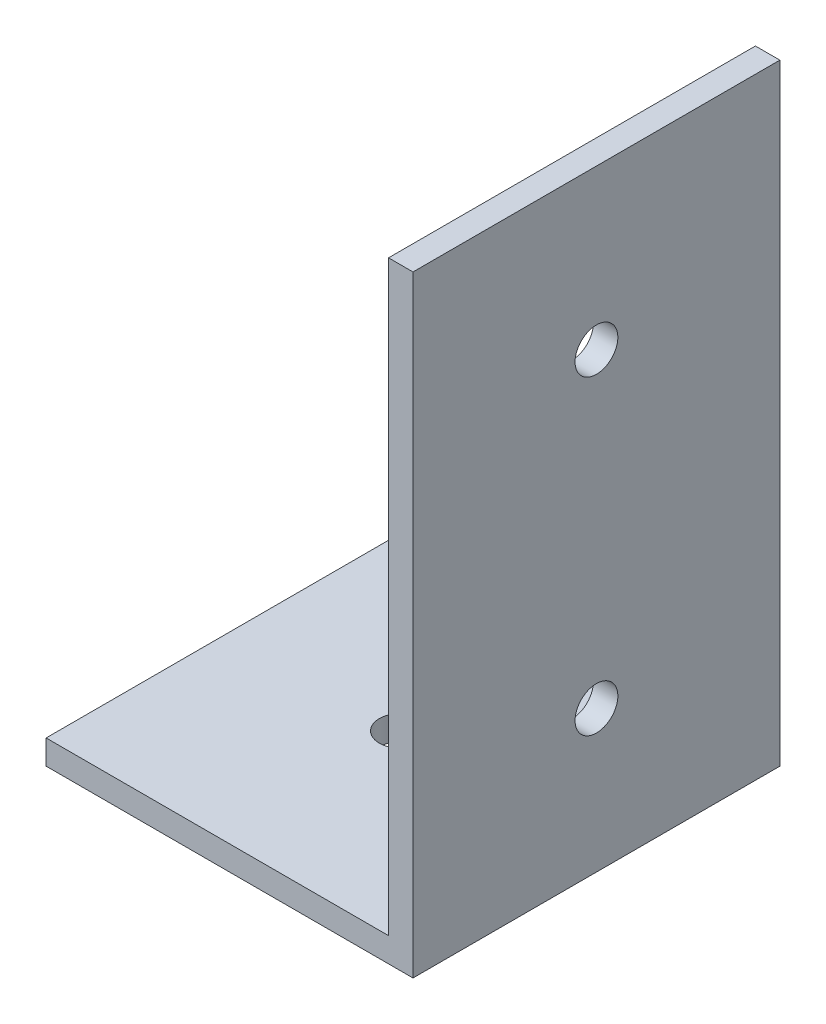
SolidWorks part; units mm, degrees
ref_plane "Piano frontale" through (0, 0, 0) normal (0, 0, 1) x (1, 0, 0)
ref_plane "Piano superiore" through (0, 0, 0) normal (0, 1, 0) x (1, 0, 0)
ref_plane "Piano destro" through (0, 0, 0) normal (1, 0, 0) x (0, 0, -1)
sketch "Schizzo1" plane through (0, 0, 0) normal (0, 0, 1) x (1, 0, 0)
  line L0 (0, 0) -> (-30, 0)
  line L1 (-30, 0) -> (-30, 2)
  line L2 (-30, 2) -> (-2, 2)
  line L3 (-2, 2) -> (-2, 50)
  line L4 (-2, 50) -> (0, 50)
  line L5 (0, 50) -> (0, 0)
  dimension "D1" = 50
  dimension "D2" = 30
  dimension "D3" = 2
extrude "Estrusione-Estrusione1" add sketch "Schizzo1" along normal blind 30
sketch "Schizzo2" plane through (-2, 0, 0) normal (-1, 0, 0) x (0, 0, 1)
  line L0 (30, 0) -> (0, 0) construction
  line L1 (15, 38.75) -> (15, 5.7333) construction
  line L2 (30, 50) -> (30, 2) construction
  line L3 (0, 50) -> (0, 2) construction
  circle A0 centre (15, 37) radius 1.75
  circle A1 centre (15, 11.6) radius 1.75
  dimension "D2" = 3.5
  dimension "D4" = 3.5
  dimension "D1" = 37
  dimension "D3" = 11.6
extrude "Taglio-Estrusione1" cut sketch "Schizzo2" against normal through all
sketch "Schizzo3" plane through (0, 2, 0) normal (0, 1, 0) x (1, 0, 0)
  line L0 (-30, -15) -> (-2, -15) construction
  line L1 (-30, -30) -> (-30, 0) construction
  line L2 (-2, -30) -> (-2, 0) construction
  line L3 (-16, 0) -> (-16, -30) construction
  line L4 (-2, 0) -> (-30, 0) construction
  line L5 (-2, -30) -> (-30, -30) construction
  circle A0 centre (-16, -15) radius 1.75
  dimension "D1" = 3.5
extrude "Taglio-Estrusione2" cut sketch "Schizzo3" against normal through all
